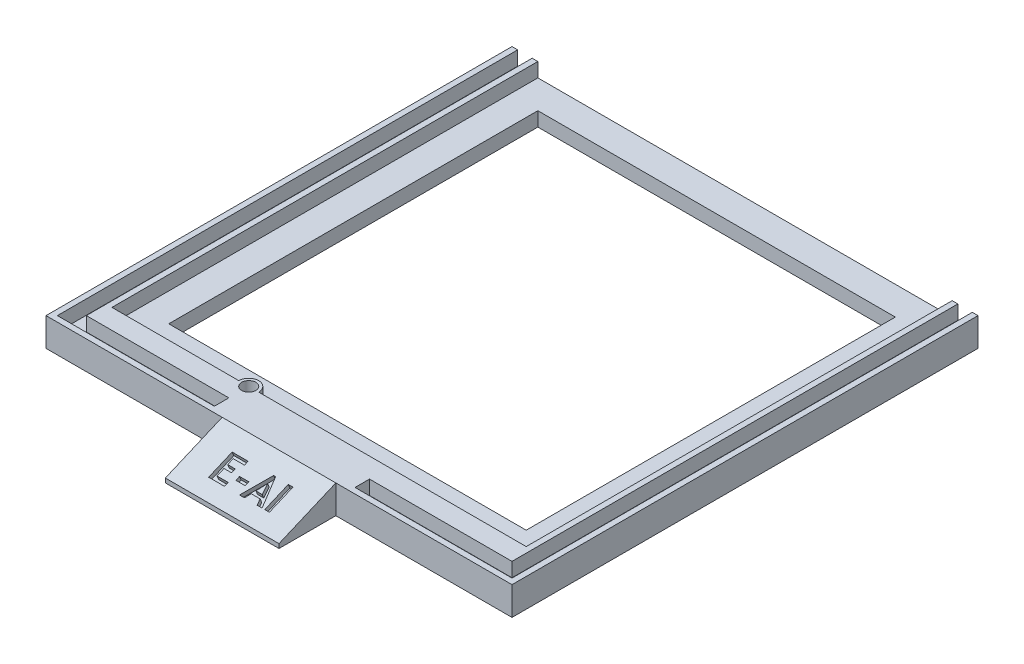
SolidWorks part; units mm, degrees
ref_plane "Front Plane" through (0, 0, 0) normal (0, 0, 1) x (1, 0, 0)
ref_plane "Top Plane" through (0, 0, 0) normal (0, 1, 0) x (1, 0, 0)
ref_plane "Right Plane" through (0, 0, 0) normal (1, 0, 0) x (0, 0, -1)
sketch "Sketch1" plane through (0, 0, 0) normal (0, 1, 0) x (1, 0, 0)
  line L1 (-82, 82) -> (82, 82)
  line L2 (-82, 82) -> (-82, -82)
  line L3 (-82, -82) -> (82, -82)
  line L4 (82, 82) -> (82, -82)
  line L5 (-82, 82) -> (82, -82) construction
  line L6 (-82, -82) -> (82, 82) construction
  point P0 (0, 0)
  dimension "D1" = 164
  dimension "D2" = 164
extrude "Boss-Extrude1" add sketch "Sketch1" along normal blind 5
sketch "Sketch2" plane through (0, 5, 0) normal (0, 1, 0) x (1, 0, 0)
  line L0 (-80, 80) -> (-80, 82)
  line L1 (-82, 82) -> (82, 82)
  line L2 (-82, 82) -> (-82, -82)
  line L3 (-82, -82) -> (-24.75, -82)
  line L4 (82, 82) -> (82, -82)
  line L5 (-82, 82) -> (82, -82) construction
  line L6 (-82, -82) -> (82, 82) construction
  line L8 (-80, 80) -> (-80, -80)
  line L9 (-80, -80) -> (-24.75, -80)
  line L10 (80, 80) -> (80, -80)
  line L11 (-80, 80) -> (80, -80) construction
  line L12 (-80, -80) -> (80, 80) construction
  line L13 (80, 80) -> (80, 82)
  line L14 (-24.75, -77.45) -> (24.75, -77.45) construction
  line L15 (-74.9, 82) -> (-74.9, -74.9)
  line L16 (-74.9, -74.9) -> (-24.75, -74.9)
  line L17 (74.9, -74.9) -> (74.9, 82)
  line L18 (-72.9, 82) -> (-72.9, -72.9)
  line L19 (-72.9, -72.9) -> (72.9, -72.9)
  line L20 (72.9, -72.9) -> (72.9, 82)
  line L21 (-24.75, -82) -> (24.75, -82)
  line L23 (-24.75, -82) -> (-24.75, -72.9)
  line L24 (24.75, -82) -> (24.75, -72.9)
  line L25 (0, -77.45) -> (0, -72.9) construction
  line L26 (24.75, -82) -> (82, -82)
  line L27 (24.75, -80) -> (80, -80)
  line L28 (-82, 82) -> (82, 82)
  line L29 (24.75, -74.9) -> (74.9, -74.9)
  point P0 (0, 0)
  point P7 (0, 0)
  dimension "D1" = 2
  dimension "D2" = 2
  dimension "D3" = 5.1
  dimension "D4" = 5.1
  dimension "D5" = 5.1
  dimension "D6" = 2
  dimension "D7" = 2
  dimension "D8" = 2
  dimension "D11" = 49.5
  dimension "D12" = 2
extrude "Boss-Extrude2" add sketch "Sketch2" along normal blind 5
sketch "Sketch3" plane through (0, 5, 0) normal (0, 1, 0) x (1, 0, 0)
  line L0 (-24.75, -67.9) -> (-24.75, -74.9) construction
  line L1 (-72.9, -72.9) -> (72.9, -72.9) construction
  circle A0 centre (-24.75, -67.9) radius 2.5
  circle A1 centre (-24.75, -67.9) radius 3.5
  dimension "D1" = 5
  dimension "D3" = 7
  dimension "D2" = 5
extrude "Boss-Extrude3" add sketch "Sketch3" along normal blind 5
sketch "Sketch5" plane through (0, 5, 0) normal (0, 1, 0) x (1, 0, 0)
  line L0 (-62.9, 72) -> (62.9, 72)
  line L1 (62.9, 72) -> (62.9, -57.9)
  line L2 (62.9, -57.9) -> (-62.9, -57.9)
  line L3 (-62.9, -57.9) -> (-62.9, 72)
  line L4 (-72.9, 82) -> (-72.9, -72.9) construction
  line L5 (72.9, -72.9) -> (72.9, 82) construction
  line L6 (72.9, 82) -> (-72.9, 82) construction
  line L7 (-72.9, -72.9) -> (72.9, -72.9) construction
  dimension "D1" = 10
  dimension "D2" = 10
  dimension "D3" = 10
  dimension "D4" = 15
extrude "Cut-Extrude1" cut sketch "Sketch5" against normal through all
chamfer "Chamfer2" distance 10 angle 45 1 edges at (0, 5, 72.9)
sketch "Sketch6" plane through (0, 0, 0) normal (1, 0, 0) x (0, 0, -1)
  line L4 (-82, 0) -> (-82, 10)
  line L6 (-102, 0) -> (-82, 0)
  line L7 (-82, 10) -> (-102, 1.5)
  line L8 (-102, 1.5) -> (-102, 0)
  dimension "D1" = 20
  dimension "D2" = 1.5
extrude "Boss-Extrude4" add sketch "Sketch6" along normal mid plane 40
sketch "Sketch7" plane through (0, -16.9382, 145.384) normal (0, -0.9203, -0.3911) x (1, 0, 0)
  line L0 (-20, -53.1396) -> (20, -53.1396) construction
  line L4 (-20, -68.8709) -> (-20, -47.1396) construction
  line L5 (20, -68.8709) -> (20, -47.1396) construction
  line L6 (20, -47.1396) -> (-20, -47.1396) construction
  text T0 "<b>E-AI</b>" font "Trebuchet MS" height 9
  dimension "D1" = 6
extrude "Cut-Extrude3" cut sketch "Sketch7" along normal blind 1.5
